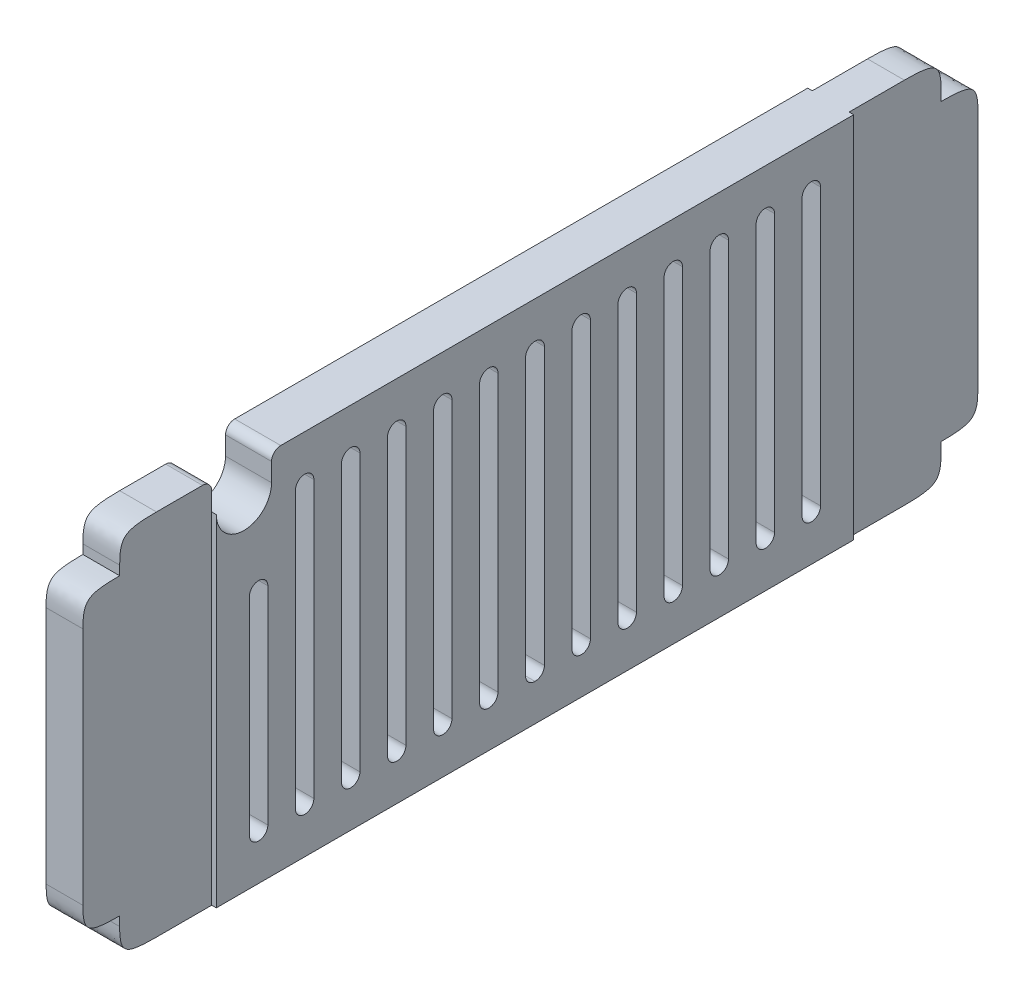
SolidWorks part; units mm, degrees
ref_plane "Front Plane" through (0, 0, 0) normal (0, 0, 1) x (1, 0, 0)
ref_plane "Top Plane" through (0, 0, 0) normal (0, 1, 0) x (1, 0, 0)
ref_plane "Right Plane" through (0, 0, 0) normal (1, 0, 0) x (0, 0, -1)
sketch "Sketch1" plane through (0, 0, 0) normal (0, 1, 0) x (1, 0, 0)
  line L0 (0, -6.35) -> (2.54, -6.35) construction
  line L1 (0, -6.35) -> (0, 0)
  line L2 (0, 0) -> (2.54, 0)
  line L3 (2.54, 0) -> (2.54, -6.35)
  line L4 (2.8575, -6.35) -> (2.54, -6.35)
  line L5 (0, -6.35) -> (-0.3175, -6.35)
  line L6 (-0.3175, -6.35) -> (-0.3175, -56.642)
  line L7 (2.8575, -6.35) -> (2.8575, -56.642)
  line L8 (-0.3175, -31.496) -> (2.8575, -31.496) construction
  line L9 (0, -56.642) -> (2.54, -56.642) construction
  line L10 (0, -56.642) -> (-0.3175, -56.642)
  line L11 (2.8575, -56.642) -> (2.54, -56.642)
  line L12 (2.54, -62.992) -> (2.54, -56.642)
  line L13 (0, -62.992) -> (2.54, -62.992)
  line L14 (0, -56.642) -> (0, -62.992)
  point P9 (1.27, -6.35)
  point P15 (1.27, -56.642)
  dimension "D1" = 3.175
  dimension "D2" = 0.3175
extrude "Boss-Extrude1" add sketch "Sketch1" along normal blind 25.4 contours L1 L2 L3 L4 L7 L11 L12 L13 L14 L10 L6 L5
sketch "Sketch2" plane through (2.54, 0, 0) normal (1, 0, 0) x (0, 0, -1)
  line L1 (-62.992, 22.86) -> (-62.992, 25.4) construction
  line L2 (-31.496, 25.4) -> (-31.496, 0) construction
  line L3 (-6.35, 25.4) -> (-56.642, 25.4) construction
  line L4 (-6.35, 0) -> (-56.642, 0) construction
  line L5 (-62.992, 22.86) -> (-65.532, 22.86)
  line L13 (-62.992, 2.54) -> (-62.992, 22.86)
  line L14 (-62.992, 25.4) -> (-62.992, 0) construction
  line L15 (-62.992, 2.54) -> (-62.992, 0) construction
  line L16 (-65.532, 22.86) -> (-65.532, 2.54)
  line L17 (-65.532, 2.54) -> (-62.992, 2.54)
  line L18 (0, 2.54) -> (0, 0) construction
  line L19 (0, 22.86) -> (0, 25.4) construction
  line L20 (2.54, 2.54) -> (0, 2.54)
  line L21 (2.54, 22.86) -> (2.54, 2.54)
  line L22 (0, 2.54) -> (0, 22.86)
  line L23 (0, 22.86) -> (2.54, 22.86)
  point P13 (-62.992, 12.7)
  point P23 (0, 12.7)
  line M9 (-62.992, 25.4) -> (-62.992, 0)
  dimension "D1" = 20.32
  dimension "D2" = 2.54
extrude "Boss-Extrude2" add sketch "Sketch2" against normal up to surface (2.54 mm away) contours M9 | L20 L22 L23 L21 region at (2.54, 12.7, 64.262) up to face at (0, 12.7, 59.817)
sketch "Sketch3" plane through (-0.3175, 0, 0) normal (-1, 0, 0) x (0, 0, 1)
  line L0 (31.496, 25.4) -> (31.496, 0) construction
  line L1 (6.35, 25.4) -> (56.642, 25.4) construction
  line L2 (6.35, 0) -> (56.642, 0) construction
  line L3 (31.496, 3.175) -> (31.496, 22.225) construction
  line L4 (31.496, 3.175) -> (31.496, 22.225) construction
  line L5 (30.861, 3.175) -> (30.861, 22.225)
  line L6 (32.131, 3.175) -> (32.131, 22.225)
  line L7 (35.306, 3.175) -> (35.306, 22.225)
  line L8 (34.036, 3.175) -> (34.036, 22.225)
  line L9 (34.671, 3.175) -> (34.671, 22.225) construction
  line L10 (38.481, 3.175) -> (38.481, 22.225)
  line L11 (37.211, 3.175) -> (37.211, 22.225)
  line L12 (37.846, 3.175) -> (37.846, 22.225) construction
  line L13 (41.656, 3.175) -> (41.656, 22.225)
  line L14 (40.386, 3.175) -> (40.386, 22.225)
  line L15 (41.021, 3.175) -> (41.021, 22.225) construction
  line L16 (44.831, 3.175) -> (44.831, 22.225)
  line L17 (43.561, 3.175) -> (43.561, 22.225)
  line L18 (44.196, 3.175) -> (44.196, 22.225) construction
  line L19 (48.006, 3.175) -> (48.006, 22.225)
  line L20 (46.736, 3.175) -> (46.736, 22.225)
  line L21 (47.371, 3.175) -> (47.371, 22.225) construction
  line L22 (51.181, 3.175) -> (51.181, 22.225)
  line L23 (49.911, 3.175) -> (49.911, 22.225)
  line L24 (50.546, 3.175) -> (50.546, 22.225) construction
  line L25 (54.356, 3.175) -> (54.356, 22.225)
  line L26 (53.086, 3.175) -> (53.086, 22.225)
  line L27 (53.721, 3.175) -> (53.721, 22.225) construction
  line L28 (28.321, 3.175) -> (28.321, 22.225) construction
  line L29 (27.686, 3.175) -> (27.686, 22.225)
  line L30 (28.956, 3.175) -> (28.956, 22.225)
  line L31 (25.146, 3.175) -> (25.146, 22.225) construction
  line L32 (24.511, 3.175) -> (24.511, 22.225)
  line L33 (25.781, 3.175) -> (25.781, 22.225)
  line L34 (21.971, 3.175) -> (21.971, 22.225) construction
  line L35 (21.336, 3.175) -> (21.336, 22.225)
  line L36 (22.606, 3.175) -> (22.606, 22.225)
  line L37 (18.796, 3.175) -> (18.796, 22.225) construction
  line L38 (18.161, 3.175) -> (18.161, 22.225)
  line L39 (19.431, 3.175) -> (19.431, 22.225)
  line L40 (15.621, 3.175) -> (15.621, 22.225) construction
  line L41 (14.986, 3.175) -> (14.986, 22.225)
  line L42 (16.256, 3.175) -> (16.256, 22.225)
  line L43 (12.446, 3.175) -> (12.446, 22.225) construction
  line L44 (11.811, 3.175) -> (11.811, 22.225)
  line L45 (13.081, 3.175) -> (13.081, 22.225)
  line L46 (9.271, 3.175) -> (9.271, 22.225) construction
  line L47 (8.636, 3.175) -> (8.636, 22.225)
  line L48 (9.906, 3.175) -> (9.906, 22.225)
  arc A0 (30.861, 3.175) -> (32.131, 3.175) centre (31.496, 3.175) ccw
  arc A1 (32.131, 22.225) -> (30.861, 22.225) centre (31.496, 22.225) ccw
  arc A2 (34.036, 3.175) -> (35.306, 3.175) centre (34.671, 3.175) ccw
  arc A3 (35.306, 22.225) -> (34.036, 22.225) centre (34.671, 22.225) ccw
  arc A4 (37.211, 3.175) -> (38.481, 3.175) centre (37.846, 3.175) ccw
  arc A5 (38.481, 22.225) -> (37.211, 22.225) centre (37.846, 22.225) ccw
  arc A6 (40.386, 3.175) -> (41.656, 3.175) centre (41.021, 3.175) ccw
  arc A7 (41.656, 22.225) -> (40.386, 22.225) centre (41.021, 22.225) ccw
  arc A8 (43.561, 3.175) -> (44.831, 3.175) centre (44.196, 3.175) ccw
  arc A9 (44.831, 22.225) -> (43.561, 22.225) centre (44.196, 22.225) ccw
  arc A10 (46.736, 3.175) -> (48.006, 3.175) centre (47.371, 3.175) ccw
  arc A11 (48.006, 22.225) -> (46.736, 22.225) centre (47.371, 22.225) ccw
  arc A12 (49.911, 3.175) -> (51.181, 3.175) centre (50.546, 3.175) ccw
  arc A13 (51.181, 22.225) -> (49.911, 22.225) centre (50.546, 22.225) ccw
  arc A14 (53.086, 3.175) -> (54.356, 3.175) centre (53.721, 3.175) ccw
  arc A15 (54.356, 22.225) -> (53.086, 22.225) centre (53.721, 22.225) ccw
  arc A16 (27.686, 3.175) -> (28.956, 3.175) centre (28.321, 3.175) ccw
  arc A17 (28.956, 22.225) -> (27.686, 22.225) centre (28.321, 22.225) ccw
  arc A18 (24.511, 3.175) -> (25.781, 3.175) centre (25.146, 3.175) ccw
  arc A19 (25.781, 22.225) -> (24.511, 22.225) centre (25.146, 22.225) ccw
  arc A20 (21.336, 3.175) -> (22.606, 3.175) centre (21.971, 3.175) ccw
  arc A21 (22.606, 22.225) -> (21.336, 22.225) centre (21.971, 22.225) ccw
  arc A22 (18.161, 3.175) -> (19.431, 3.175) centre (18.796, 3.175) ccw
  arc A23 (19.431, 22.225) -> (18.161, 22.225) centre (18.796, 22.225) ccw
  arc A24 (14.986, 3.175) -> (16.256, 3.175) centre (15.621, 3.175) ccw
  arc A25 (16.256, 22.225) -> (14.986, 22.225) centre (15.621, 22.225) ccw
  arc A26 (11.811, 3.175) -> (13.081, 3.175) centre (12.446, 3.175) ccw
  arc A27 (13.081, 22.225) -> (11.811, 22.225) centre (12.446, 22.225) ccw
  arc A28 (8.636, 3.175) -> (9.906, 3.175) centre (9.271, 3.175) ccw
  arc A29 (9.906, 22.225) -> (8.636, 22.225) centre (9.271, 22.225) ccw
  point P6 (31.496, 12.7)
  point P9 (31.496, 12.7)
  point P15 (28.321, 12.7)
  point P16 (34.671, 12.7)
  point P23 (37.846, 12.7)
  point P30 (41.021, 12.7)
  point P37 (44.196, 12.7)
  point P44 (47.371, 12.7)
  point P51 (50.546, 12.7)
  point P58 (53.721, 12.7)
  point P71 (25.146, 12.7)
  point P78 (21.971, 12.7)
  point P85 (18.796, 12.7)
  point P92 (15.621, 12.7)
  point P99 (12.446, 12.7)
  point P106 (9.271, 12.7)
  dimension "D1" = 19.05
  dimension "D2" = 1.27
  dimension "D4" = 3.175
  dimension "D6" = 3.175
  dimension "D3" = 8
  dimension "D5" = 8
extrude "Cut-Extrude1" cut sketch "Sketch3" against normal through all both and the other way through all
fillet "Fillet1" radius 1.905 4 edges at (1.27, 22.86, 65.532) (1.27, 2.54, -2.54) (1.27, 25.4, 62.992) (1.27, 0, 0) second distance 2.54 conic rho 0.65 first distance on face at (1.27, 12.7, 65.532) first distance on face at (1.27, 12.7, -2.54) first distance on face at (1.27, 24.13, 62.992) first distance on face at (1.27, 1.27, 0)
fillet "Fillet2" radius 2.54 4 edges at (1.27, 0, 62.992) (1.27, 2.54, 65.532) (1.27, 25.4, 0) (1.27, 22.86, -2.54) second distance 1.905 conic rho 0.65 first distance on face at (1.1642, 0, 31.9193) first distance on face at (1.27, 2.54, 64.262) first distance on face at (1.1642, 25.4, 31.0727) first distance on face at (1.27, 22.86, -1.27)
sketch "Sketch4" plane through (-0.3175, 0, 0) normal (-1, 0, 0) x (0, 0, 1)
  line L0 (6.35, 25.4) -> (25.146, 25.4) construction
  line L1 (6.35, 25.4) -> (56.642, 25.4) construction
  line L2 (25.146, 25.4) -> (25.146, 0)
  line L3 (6.35, 0) -> (56.642, 0) construction
  line L4 (25.146, 0) -> (68.2439, 0)
  line L5 (68.2439, 0) -> (68.2439, 25.4)
  line L6 (68.2439, 25.4) -> (25.146, 25.4)
  dimension "D1" = 18.796
extrude "Cut-Extrude2" cut sketch "Sketch4" against normal through all both and the other way through all
sketch "Sketch5" plane through (-0.3175, 0, 0) normal (-1, 0, 0) x (0, 0, 1)
  line L0 (25.146, 25.4) -> (25.146, 22.86) construction
  line L1 (21.336, 22.225) -> (21.336, 3.175) construction
  line L2 (22.606, 3.175) -> (22.606, 22.225) construction
  line L3 (21.336, 22.225) -> (21.336, 3.175)
  line L4 (22.606, 3.175) -> (22.606, 22.225)
  line L5 (18.161, 22.225) -> (18.161, 3.175)
  line L6 (19.431, 3.175) -> (19.431, 22.225)
  line L7 (6.35, 0) -> (25.146, 0)
  line L8 (25.146, 0) -> (25.146, 2.54)
  line L9 (24.511, 3.175) -> (24.511, 22.225)
  line L10 (25.146, 22.86) -> (25.146, 25.4)
  line L11 (25.146, 25.4) -> (6.35, 25.4)
  line L12 (6.35, 25.4) -> (6.35, 0)
  line L13 (6.35, 0) -> (43.942, 0)
  line L14 (25.146, 0) -> (25.146, 2.54)
  line L15 (24.511, 3.175) -> (24.511, 22.225)
  line L16 (25.146, 22.86) -> (25.146, 25.4)
  line L17 (43.942, 25.4) -> (6.35, 25.4)
  line L18 (6.35, 25.4) -> (6.35, 0)
  line L19 (14.986, 22.225) -> (14.986, 3.175)
  line L20 (16.256, 3.175) -> (16.256, 22.225)
  line L21 (11.811, 22.225) -> (11.811, 3.175)
  line L22 (13.081, 3.175) -> (13.081, 22.225)
  line L23 (8.636, 22.225) -> (8.636, 3.175)
  line L24 (9.906, 3.175) -> (9.906, 22.225)
  line L25 (40.386, 3.175) -> (40.386, 22.225)
  line L26 (41.656, 22.225) -> (41.656, 3.175)
  line L27 (37.211, 3.175) -> (37.211, 22.225)
  line L28 (38.481, 22.225) -> (38.481, 3.175)
  line L29 (34.036, 3.175) -> (34.036, 22.225)
  line L30 (35.306, 22.225) -> (35.306, 3.175)
  line L31 (43.942, 25.4) -> (43.942, 0)
  line L32 (25.781, 3.175) -> (25.781, 22.225)
  line L33 (30.861, 3.175) -> (30.861, 22.225)
  line L34 (32.131, 22.225) -> (32.131, 3.175)
  line L35 (27.686, 3.175) -> (27.686, 22.225)
  line L36 (28.956, 22.225) -> (28.956, 3.175)
  arc A0 (22.606, 22.225) -> (21.336, 22.225) centre (21.971, 22.225) ccw construction
  arc A1 (21.336, 3.175) -> (22.606, 3.175) centre (21.971, 3.175) ccw construction
  arc A2 (24.511, 3.175) -> (25.146, 2.54) centre (25.146, 3.175) ccw
  arc A3 (25.146, 22.86) -> (24.511, 22.225) centre (25.146, 22.225) ccw
  arc A4 (24.511, 3.175) -> (25.781, 3.175) centre (25.146, 3.175) ccw
  arc A5 (25.781, 22.225) -> (24.511, 22.225) centre (25.146, 22.225) ccw
  arc A6 (22.606, 22.225) -> (21.336, 22.225) centre (21.971, 22.225) ccw
  arc A7 (21.336, 3.175) -> (22.606, 3.175) centre (21.971, 3.175) ccw
  arc A8 (19.431, 22.225) -> (18.161, 22.225) centre (18.796, 22.225) ccw
  arc A9 (18.161, 3.175) -> (19.431, 3.175) centre (18.796, 3.175) ccw
  arc A10 (16.256, 22.225) -> (14.986, 22.225) centre (15.621, 22.225) ccw
  arc A11 (14.986, 3.175) -> (16.256, 3.175) centre (15.621, 3.175) ccw
  arc A12 (13.081, 22.225) -> (11.811, 22.225) centre (12.446, 22.225) ccw
  arc A13 (11.811, 3.175) -> (13.081, 3.175) centre (12.446, 3.175) ccw
  arc A14 (9.906, 22.225) -> (8.636, 22.225) centre (9.271, 22.225) ccw
  arc A15 (8.636, 3.175) -> (9.906, 3.175) centre (9.271, 3.175) ccw
  arc A16 (41.656, 3.175) -> (40.386, 3.175) centre (41.021, 3.175) cw
  arc A17 (40.386, 22.225) -> (41.656, 22.225) centre (41.021, 22.225) cw
  arc A18 (38.481, 3.175) -> (37.211, 3.175) centre (37.846, 3.175) cw
  arc A19 (37.211, 22.225) -> (38.481, 22.225) centre (37.846, 22.225) cw
  arc A20 (35.306, 3.175) -> (34.036, 3.175) centre (34.671, 3.175) cw
  arc A21 (34.036, 22.225) -> (35.306, 22.225) centre (34.671, 22.225) cw
  arc A22 (32.131, 3.175) -> (30.861, 3.175) centre (31.496, 3.175) cw
  arc A23 (30.861, 22.225) -> (32.131, 22.225) centre (31.496, 22.225) cw
  arc A24 (28.956, 3.175) -> (27.686, 3.175) centre (28.321, 3.175) cw
  arc A25 (27.686, 22.225) -> (28.956, 22.225) centre (28.321, 22.225) cw
  line M50 (25.146, 0) -> (25.146, 2.54)
  line M54 (25.146, 22.86) -> (25.146, 25.4)
  dimension "D3" = 1.905
  dimension "D1" = 0
  dimension "D2" = 5
extrude "Boss-Extrude3" add sketch "Sketch5" against normal up to surface (3.175 mm away) contours A5 L32 A4 L13 L31 L17 L25 A17 L26 A16 L27 A19 L28 A18 L29 A21 L30 A20 L33 A23 L34 A22 L35 A25 L36 A24 M50 M54 region at (-0.3175, 1.27, 25.462) up to face at (2.8575, 12.7, 20.2554)
sketch "Sketch7" plane through (2.54, 0, 0) normal (1, 0, 0) x (0, 0, -1)
  line L0 (-25.146, 25.4) -> (-25.146, 0) construction
  line L1 (-6.35, 25.4) -> (-43.942, 25.4) construction
  line L2 (-6.35, 0) -> (-43.942, 0) construction
  line L3 (-52.832, 4.445) -> (-52.832, 20.955)
  line L4 (-50.292, 1.905) -> (-50.292, 2.54)
  line L5 (-43.942, 0) -> (-47.752, 0)
  line L6 (0, 22.86) -> (0, 23.495)
  line L7 (-2.54, 25.4) -> (-6.35, 25.4)
  line L8 (-6.35, 25.4) -> (-6.35, 0)
  line L9 (-6.35, 0) -> (-2.54, 0)
  line L10 (0, 1.905) -> (0, 2.54)
  line L11 (2.54, 4.445) -> (2.54, 20.955)
  line L12 (0, 22.86) -> (0, 23.495)
  line L13 (-2.54, 25.4) -> (-6.35, 25.4)
  line L14 (-6.35, 25.4) -> (-6.35, 0)
  line L15 (-6.35, 0) -> (-2.54, 0)
  line L16 (0, 1.905) -> (0, 2.54)
  line L17 (2.54, 4.445) -> (2.54, 20.955)
  line L18 (-43.942, 25.4) -> (-43.942, 0)
  line L19 (-47.752, 25.4) -> (-43.942, 25.4)
  line L20 (-50.292, 22.86) -> (-50.292, 23.495)
  spline S0 degree 2 poles (-52.832, 20.955) (-52.832, 21.5663) (-52.7501, 21.9126) (-52.6865, 22.1813) (-52.561, 22.3519) (-52.4246, 22.5373) (-52.1842, 22.644) (-51.8674, 22.7847) (-51.2479, 22.8311) (-50.8627, 22.86) (-50.292, 22.86) knots 0 0 0 0.25 0.25 0.375 0.375 0.5 0.5 0.75 0.75 1 1 1
  spline S1 degree 2 poles (-50.292, 2.54) (-50.8585, 2.54) (-51.243, 2.5685) (-51.5105, 2.5884) (-51.7145, 2.6236) (-51.9898, 2.6712) (-52.1773, 2.753) (-52.4197, 2.8586) (-52.5582, 3.0444) (-52.6854, 3.2149) (-52.75, 3.487) (-52.832, 3.8326) (-52.832, 4.445) knots 0 0 0 0.25 0.25 0.375 0.375 0.5 0.5 0.625 0.625 0.75 0.75 1 1 1
  spline S2 degree 2 poles (-47.752, 0) (-48.3185, 0) (-48.703, 0.0285) (-48.9705, 0.0484) (-49.1745, 0.0836) (-49.4498, 0.1312) (-49.6373, 0.213) (-49.8797, 0.3186) (-50.0182, 0.5044) (-50.1454, 0.6749) (-50.21, 0.947) (-50.292, 1.2926) (-50.292, 1.905) knots 0 0 0 0.25 0.25 0.375 0.375 0.5 0.5 0.625 0.625 0.75 0.75 1 1 1
  spline S3 degree 2 poles (-50.292, 23.495) (-50.292, 24.1063) (-50.2101, 24.4526) (-50.1465, 24.7213) (-50.021, 24.8919) (-49.8846, 25.0773) (-49.6442, 25.184) (-49.3274, 25.3247) (-48.7079, 25.3711) (-48.3227, 25.4) (-47.752, 25.4) knots 0 0 0 0.25 0.25 0.375 0.375 0.5 0.5 0.75 0.75 1 1 1
  spline S4 degree 2 poles (-1140.7767, -3810.167) (9.6672, -16.7611) (-0.0819, 24.4526) (-0.1455, 24.7213) (-0.271, 24.8919) (-0.4074, 25.0773) (-0.6478, 25.184) (-0.9646, 25.3247) (-1.5841, 25.3711) (-57.0505, 29.5301) (-3958.5798, -565.1683) knots -29.501187 -29.501187 -29.501187 0.25 0.25 0.375 0.375 0.5 0.5 0.75 0.75 36.747836 36.747836 36.747836 only from (0, 23.495) to (-2.54, 25.4)
  spline S5 degree 2 poles (-3958.0281, 594.1974) (-57.4767, -4.1164) (-1.589, 0.0285) (-1.3215, 0.0484) (-1.1175, 0.0836) (-0.8422, 0.1312) (-0.6547, 0.213) (-0.4123, 0.3186) (-0.2738, 0.5044) (-0.1466, 0.6749) (-0.082, 0.947) (9.6475, 41.939) (-1134.6947, 3837.3785) knots -36.087343 -36.087343 -36.087343 0.25 0.25 0.375 0.375 0.5 0.5 0.625 0.625 0.75 0.75 30.403939 30.403939 30.403939 only from (-2.54, 0) to (0, 1.905)
  spline S6 degree 2 poles (-3955.4881, 596.7374) (-54.9367, -1.5764) (0.951, 2.5685) (1.2185, 2.5884) (1.4225, 2.6236) (1.6978, 2.6712) (1.8853, 2.753) (2.1277, 2.8586) (2.2662, 3.0444) (2.3934, 3.2149) (2.458, 3.487) (12.1875, 44.479) (-1132.1547, 3839.9185) knots -36.087343 -36.087343 -36.087343 0.25 0.25 0.375 0.375 0.5 0.5 0.625 0.625 0.75 0.75 30.403939 30.403939 30.403939 only from (0, 2.54) to (2.54, 4.445)
  spline S7 degree 2 poles (-1138.2367, -3812.707) (12.2072, -19.3011) (2.4581, 21.9126) (2.3945, 22.1813) (2.269, 22.3519) (2.1326, 22.5373) (1.8922, 22.644) (1.5754, 22.7847) (0.9559, 22.8311) (-54.5105, 26.9901) (-3956.0398, -567.7083) knots -29.501187 -29.501187 -29.501187 0.25 0.25 0.375 0.375 0.5 0.5 0.75 0.75 36.747836 36.747836 36.747836 only from (2.54, 20.955) to (0, 22.86)
  spline S8 degree 2 poles (0, 23.495) (0, 24.1063) (-0.0819, 24.4526) (-0.1455, 24.7213) (-0.271, 24.8919) (-0.4074, 25.0773) (-0.6478, 25.184) (-0.9646, 25.3247) (-1.5841, 25.3711) (-1.9693, 25.4) (-2.54, 25.4) knots 0 0 0 0.25 0.25 0.375 0.375 0.5 0.5 0.75 0.75 1 1 1
  spline S9 degree 2 poles (-2.54, 0) (-1.9735, 0) (-1.589, 0.0285) (-1.3215, 0.0484) (-1.1175, 0.0836) (-0.8422, 0.1312) (-0.6547, 0.213) (-0.4123, 0.3186) (-0.2738, 0.5044) (-0.1466, 0.6749) (-0.082, 0.947) (0, 1.2926) (0, 1.905) knots 0 0 0 0.25 0.25 0.375 0.375 0.5 0.5 0.625 0.625 0.75 0.75 1 1 1
  spline S10 degree 2 poles (0, 2.54) (0.5665, 2.54) (0.951, 2.5685) (1.2185, 2.5884) (1.4225, 2.6236) (1.6978, 2.6712) (1.8853, 2.753) (2.1277, 2.8586) (2.2662, 3.0444) (2.3934, 3.2149) (2.458, 3.487) (2.54, 3.8326) (2.54, 4.445) knots 0 0 0 0.25 0.25 0.375 0.375 0.5 0.5 0.625 0.625 0.75 0.75 1 1 1
  spline S11 degree 2 poles (2.54, 20.955) (2.54, 21.5663) (2.4581, 21.9126) (2.3945, 22.1813) (2.269, 22.3519) (2.1326, 22.5373) (1.8922, 22.644) (1.5754, 22.7847) (0.9559, 22.8311) (0.5707, 22.86) (0, 22.86) knots 0 0 0 0.25 0.25 0.375 0.375 0.5 0.5 0.75 0.75 1 1 1
  dimension "D1" = 0
extrude "Boss-Extrude4" add sketch "Sketch7" against normal up to surface (2.54 mm away) up to face at (0, 12.319, 1.651)
sketch "Sketch9" plane through (0, 25.4, 0) normal (0, 1, 0) x (1, 0, 0)
  line L0 (2.54, 2.54) -> (2.54, -31.5081) construction
  line L1 (2.54, -31.5081) -> (13.8841, -31.5081)
  line L2 (13.8841, -31.5081) -> (13.8841, -57.1564)
  line L3 (13.8841, -57.1564) -> (-12.4241, -57.1564)
  line L4 (-12.4241, -57.1564) -> (-12.4241, -31.5081)
  line L5 (-12.4241, -31.5081) -> (2.54, -31.5081)
  dimension "D1" = 34.0481
extrude "Cut-Extrude3" cut sketch "Sketch9" against normal through all
sketch "Sketch10" plane through (-0.3175, 0, 0) normal (-1, 0, 0) x (0, 0, 1)
  line L0 (27.686, 3.175) -> (27.686, 22.225) construction
  line L1 (28.956, 22.225) -> (28.956, 3.175) construction
  line L2 (27.686, 3.175) -> (27.686, 22.225)
  line L3 (28.956, 22.225) -> (28.956, 3.175)
  line L4 (24.511, 3.175) -> (24.511, 22.225)
  line L5 (25.781, 22.225) -> (25.781, 3.175)
  line L6 (6.35, 0) -> (31.5081, 0)
  line L7 (31.5081, 0) -> (31.5081, 2.5401)
  line L8 (30.861, 3.175) -> (30.861, 22.225)
  line L9 (31.5081, 22.8599) -> (31.5081, 25.4)
  line L10 (31.5081, 25.4) -> (6.35, 25.4)
  line L11 (6.35, 25.4) -> (6.35, 0)
  line L12 (6.35, 0) -> (56.6662, 0)
  line L13 (31.5081, 0) -> (31.5081, 2.5401)
  line L14 (30.861, 3.175) -> (30.861, 22.225)
  line L15 (31.5081, 22.8599) -> (31.5081, 25.4)
  line L16 (56.6662, 25.4) -> (6.35, 25.4)
  line L17 (6.35, 25.4) -> (6.35, 0)
  line L18 (21.336, 3.175) -> (21.336, 22.225)
  line L19 (22.606, 22.225) -> (22.606, 3.175)
  line L20 (18.161, 3.175) -> (18.161, 22.225)
  line L21 (19.431, 22.225) -> (19.431, 3.175)
  line L22 (14.986, 3.175) -> (14.986, 22.225)
  line L23 (16.256, 22.225) -> (16.256, 3.175)
  line L24 (11.811, 3.175) -> (11.811, 22.225)
  line L25 (13.081, 22.225) -> (13.081, 3.175)
  line L26 (8.636, 3.175) -> (8.636, 22.225)
  line L27 (9.906, 22.225) -> (9.906, 3.175)
  line L28 (53.1102, 22.225) -> (53.1102, 3.175)
  line L29 (54.3802, 3.175) -> (54.3802, 22.225)
  line L30 (49.9352, 22.225) -> (49.9352, 3.175)
  line L31 (51.2052, 3.175) -> (51.2052, 22.225)
  line L32 (46.7602, 22.225) -> (46.7602, 3.175)
  line L33 (48.0302, 3.175) -> (48.0302, 22.225)
  line L34 (43.5852, 22.225) -> (43.5852, 3.175)
  line L35 (44.8552, 3.175) -> (44.8552, 22.225)
  line L36 (40.4102, 22.225) -> (40.4102, 3.175)
  line L37 (41.6802, 3.175) -> (41.6802, 22.225)
  line L38 (37.2352, 22.225) -> (37.2352, 3.175)
  line L39 (38.5052, 3.175) -> (38.5052, 22.225)
  line L40 (34.0602, 22.225) -> (34.0602, 3.175)
  line L41 (35.3302, 3.175) -> (35.3302, 22.225)
  line L42 (56.6662, 25.4) -> (56.6662, 0)
  line L43 (32.1552, 3.175) -> (32.1552, 22.225)
  arc A0 (28.956, 22.225) -> (27.686, 22.225) centre (28.321, 22.225) ccw construction
  arc A1 (27.686, 3.175) -> (28.956, 3.175) centre (28.321, 3.175) ccw construction
  arc A2 (30.861, 3.175) -> (31.5081, 2.5401) centre (31.496, 3.175) ccw
  arc A3 (31.5081, 22.8599) -> (30.861, 22.225) centre (31.496, 22.225) ccw
  arc A4 (30.861, 3.175) -> (31.5081, 2.5401) centre (31.496, 3.175) ccw
  arc A5 (31.5081, 22.8599) -> (30.861, 22.225) centre (31.496, 22.225) ccw
  arc A6 (28.956, 22.225) -> (27.686, 22.225) centre (28.321, 22.225) ccw
  arc A7 (27.686, 3.175) -> (28.956, 3.175) centre (28.321, 3.175) ccw
  arc A8 (25.781, 22.225) -> (24.511, 22.225) centre (25.146, 22.225) ccw
  arc A9 (24.511, 3.175) -> (25.781, 3.175) centre (25.146, 3.175) ccw
  arc A10 (22.606, 22.225) -> (21.336, 22.225) centre (21.971, 22.225) ccw
  arc A11 (21.336, 3.175) -> (22.606, 3.175) centre (21.971, 3.175) ccw
  arc A12 (19.431, 22.225) -> (18.161, 22.225) centre (18.796, 22.225) ccw
  arc A13 (18.161, 3.175) -> (19.431, 3.175) centre (18.796, 3.175) ccw
  arc A14 (16.256, 22.225) -> (14.986, 22.225) centre (15.621, 22.225) ccw
  arc A15 (14.986, 3.175) -> (16.256, 3.175) centre (15.621, 3.175) ccw
  arc A16 (13.081, 22.225) -> (11.811, 22.225) centre (12.446, 22.225) ccw
  arc A17 (11.811, 3.175) -> (13.081, 3.175) centre (12.446, 3.175) ccw
  arc A18 (9.906, 22.225) -> (8.636, 22.225) centre (9.271, 22.225) ccw
  arc A19 (8.636, 3.175) -> (9.906, 3.175) centre (9.271, 3.175) ccw
  arc A20 (54.3802, 3.175) -> (53.1102, 3.175) centre (53.7452, 3.175) cw
  arc A21 (53.1102, 22.225) -> (54.3802, 22.225) centre (53.7452, 22.225) cw
  arc A22 (51.2052, 3.175) -> (49.9352, 3.175) centre (50.5702, 3.175) cw
  arc A23 (49.9352, 22.225) -> (51.2052, 22.225) centre (50.5702, 22.225) cw
  arc A24 (48.0302, 3.175) -> (46.7602, 3.175) centre (47.3952, 3.175) cw
  arc A25 (46.7602, 22.225) -> (48.0302, 22.225) centre (47.3952, 22.225) cw
  arc A26 (44.8552, 3.175) -> (43.5852, 3.175) centre (44.2202, 3.175) cw
  arc A27 (43.5852, 22.225) -> (44.8552, 22.225) centre (44.2202, 22.225) cw
  arc A28 (41.6802, 3.175) -> (40.4102, 3.175) centre (41.0452, 3.175) cw
  arc A29 (40.4102, 22.225) -> (41.6802, 22.225) centre (41.0452, 22.225) cw
  arc A30 (38.5052, 3.175) -> (37.2352, 3.175) centre (37.8702, 3.175) cw
  arc A31 (37.2352, 22.225) -> (38.5052, 22.225) centre (37.8702, 22.225) cw
  arc A32 (35.3302, 3.175) -> (34.0602, 3.175) centre (34.6952, 3.175) cw
  arc A33 (34.0602, 22.225) -> (35.3302, 22.225) centre (34.6952, 22.225) cw
  arc A34 (31.5081, 22.8599) -> (32.1552, 22.225) centre (31.5202, 22.225) cw
  arc A35 (32.1552, 3.175) -> (31.5081, 2.5401) centre (31.5202, 3.175) cw
  dimension "D3" = 1.905
  dimension "D1" = 0
  dimension "D2" = 7
extrude "Boss-Extrude5" add sketch "Sketch10" against normal up to surface (3.175 mm away) contours L42 L12 L17 L16 | L26 A18 L27 A19 | L24 A16 L25 A17 | L22 A14 L23 A15 | L20 A12 L21 A13 | L18 A10 L19 A11 | L4 A8 L5 A9 | A6 L2 A7 L3 | A20 L28 A21 L29 | A22 L30 A23 L31 | A24 L32 A25 L33 | A26 L34 A27 L35 | A28 L36 A29 L37 | A30 L38 A31 L39 | A32 L40 A33 L41 up to face at (2.8575, 12.7, 25.0235)
sketch "Sketch11" plane through (-0.3175, 0, 0) normal (-1, 0, 0) x (0, 0, 1)
  line L0 (27.686, 3.175) -> (27.686, 22.225) construction
  line L1 (28.956, 22.225) -> (28.956, 3.175) construction
  line L2 (27.686, 3.175) -> (27.686, 22.225)
  line L3 (28.956, 22.225) -> (28.956, 3.175)
  line L4 (32.131, 22.225) -> (32.131, 3.175)
  line L5 (30.861, 3.175) -> (30.861, 22.225)
  arc A0 (27.686, 3.175) -> (28.956, 3.175) centre (28.321, 3.175) ccw construction
  arc A1 (28.956, 22.225) -> (27.686, 22.225) centre (28.321, 22.225) ccw construction
  arc A2 (27.686, 3.175) -> (28.956, 3.175) centre (28.321, 3.175) ccw
  arc A3 (28.956, 22.225) -> (27.686, 22.225) centre (28.321, 22.225) ccw
  arc A4 (30.861, 3.175) -> (32.131, 3.175) centre (31.496, 3.175) ccw
  arc A5 (32.131, 22.225) -> (30.861, 22.225) centre (31.496, 22.225) ccw
  dimension "D2" = 1.905
  dimension "D1" = 2
extrude "Cut-Extrude4" cut sketch "Sketch11" against normal through all
sketch "Sketch12" plane through (0, 0, 0) normal (-1, 0, 0) x (0, 0, 1)
  line L0 (56.6662, 25.4) -> (56.6662, 0) construction
  line L1 (31.5081, 0) -> (31.5081, 25.4) construction
  line L2 (6.35, 0) -> (56.6662, 0) construction
  line L3 (6.35, 25.4) -> (56.6662, 25.4) construction
  line L4 (56.6662, 0) -> (56.6662, 25.4)
  line L5 (60.4762, 0) -> (56.6662, 0)
  line L6 (6.35, 25.4) -> (2.54, 25.4)
  line L7 (0, 23.495) -> (0, 22.86)
  line L8 (-2.54, 20.955) -> (-2.54, 4.445)
  line L9 (0, 2.54) -> (0, 1.905)
  line L10 (2.54, 0) -> (6.35, 0)
  line L11 (6.35, 0) -> (6.35, 25.4)
  line L12 (6.35, 25.4) -> (2.54, 25.4)
  line L13 (0, 23.495) -> (0, 22.86)
  line L14 (-2.54, 20.955) -> (-2.54, 4.445)
  line L15 (0, 2.54) -> (0, 1.905)
  line L16 (2.54, 0) -> (6.35, 0)
  line L17 (6.35, 0) -> (6.35, 25.4)
  line L18 (63.0162, 2.54) -> (63.0162, 1.905)
  line L19 (65.5562, 20.955) -> (65.5562, 4.445)
  line L20 (63.0162, 23.495) -> (63.0162, 22.86)
  line L21 (56.6662, 25.4) -> (60.4762, 25.4)
  spline S0 degree 2 poles (63.0162, 1.905) (63.0162, 1.2938) (62.9343, 0.9474) (62.8708, 0.6787) (62.7452, 0.5081) (62.6088, 0.3227) (62.3684, 0.216) (62.1827, 0.1335) (61.9072, 0.0851) (61.703, 0.0492) (61.4321, 0.0289) (61.047, 0) (60.4762, 0) knots 0 0 0 0.25 0.25 0.375 0.375 0.5 0.5 0.625 0.625 0.75 0.75 1 1 1
  spline S1 degree 2 poles (65.5562, 4.445) (65.5562, 3.8338) (65.4743, 3.4874) (65.4108, 3.2187) (65.2852, 3.0481) (65.1488, 2.8627) (64.9084, 2.756) (64.7227, 2.6735) (64.4472, 2.6251) (64.243, 2.5892) (63.9721, 2.5689) (63.587, 2.54) (63.0162, 2.54) knots 0 0 0 0.25 0.25 0.375 0.375 0.5 0.5 0.625 0.625 0.75 0.75 1 1 1
  spline S2 degree 2 poles (63.0162, 22.86) (63.5827, 22.86) (63.9672, 22.8315) (64.5833, 22.7858) (64.9016, 22.647) (65.1439, 22.5414) (65.2825, 22.3556) (65.4096, 22.1851) (65.4742, 21.913) (65.5562, 21.5674) (65.5562, 20.955) knots 0 0 0 0.25 0.25 0.5 0.5 0.625 0.625 0.75 0.75 1 1 1
  spline S3 degree 2 poles (60.4762, 25.4) (61.0427, 25.4) (61.4272, 25.3715) (62.0433, 25.3258) (62.3616, 25.187) (62.6039, 25.0814) (62.7425, 24.8956) (62.8696, 24.7251) (62.9342, 24.453) (63.0162, 24.1074) (63.0162, 23.495) knots 0 0 0 0.25 0.25 0.5 0.5 0.625 0.625 0.75 0.75 1 1 1
  spline S4 degree 2 poles (3957.9993, -568.8296) (57.479, 29.5165) (1.589, 25.3715) (0.9729, 25.3258) (0.6547, 25.187) (0.4123, 25.0814) (0.2738, 24.8956) (0.1466, 24.7251) (0.082, 24.453) (-9.6473, -16.5376) (1134.6606, -3812.0474) knots -36.08832 -36.08832 -36.08832 0.25 0.25 0.5 0.5 0.625 0.625 0.75 0.75 30.403498 30.403498 30.403498 only from (2.54, 25.4) to (0, 23.495)
  spline S5 degree 2 poles (3955.4593, -571.3696) (54.939, 26.9765) (-0.951, 22.8315) (-1.5671, 22.7858) (-1.8853, 22.647) (-2.1277, 22.5414) (-2.2662, 22.3556) (-2.3934, 22.1851) (-2.458, 21.913) (-12.1873, -19.0776) (1132.1206, -3814.5874) knots -36.08832 -36.08832 -36.08832 0.25 0.25 0.5 0.5 0.625 0.625 0.75 0.75 30.403498 30.403498 30.403498 only from (0, 22.86) to (-2.54, 20.955)
  spline S6 degree 2 poles (1138.4936, 3838.0156) (-12.2083, 44.7096) (-2.4581, 3.4874) (-2.3945, 3.2187) (-2.269, 3.0481) (-2.1326, 2.8627) (-1.8922, 2.756) (-1.7065, 2.6735) (-1.4309, 2.6251) (-1.2268, 2.5892) (-0.9559, 2.5689) (54.4976, -1.5894) (3956.0427, 592.9229) knots -29.504508 -29.504508 -29.504508 0.25 0.25 0.375 0.375 0.5 0.5 0.625 0.625 0.75 0.75 36.742225 36.742225 36.742225 only from (-2.54, 4.445) to (0, 2.54)
  spline S7 degree 2 poles (1141.0336, 3835.4756) (-9.6683, 42.1696) (0.0819, 0.9474) (0.1455, 0.6787) (0.271, 0.5081) (0.4074, 0.3227) (0.6478, 0.216) (0.8335, 0.1335) (1.1091, 0.0851) (1.3132, 0.0492) (1.5841, 0.0289) (57.0376, -4.1294) (3958.5827, 590.3829) knots -29.504508 -29.504508 -29.504508 0.25 0.25 0.375 0.375 0.5 0.5 0.625 0.625 0.75 0.75 36.742225 36.742225 36.742225 only from (0, 1.905) to (2.54, 0)
  spline S8 degree 2 poles (2.54, 25.4) (1.9735, 25.4) (1.589, 25.3715) (0.9729, 25.3258) (0.6547, 25.187) (0.4123, 25.0814) (0.2738, 24.8956) (0.1466, 24.7251) (0.082, 24.453) (0, 24.1074) (0, 23.495) knots 0 0 0 0.25 0.25 0.5 0.5 0.625 0.625 0.75 0.75 1 1 1
  spline S9 degree 2 poles (0, 22.86) (-0.5665, 22.86) (-0.951, 22.8315) (-1.5671, 22.7858) (-1.8853, 22.647) (-2.1277, 22.5414) (-2.2662, 22.3556) (-2.3934, 22.1851) (-2.458, 21.913) (-2.54, 21.5674) (-2.54, 20.955) knots 0 0 0 0.25 0.25 0.5 0.5 0.625 0.625 0.75 0.75 1 1 1
  spline S10 degree 2 poles (-2.54, 4.445) (-2.54, 3.8338) (-2.4581, 3.4874) (-2.3945, 3.2187) (-2.269, 3.0481) (-2.1326, 2.8627) (-1.8922, 2.756) (-1.7065, 2.6735) (-1.4309, 2.6251) (-1.2268, 2.5892) (-0.9559, 2.5689) (-0.5707, 2.54) (0, 2.54) knots 0 0 0 0.25 0.25 0.375 0.375 0.5 0.5 0.625 0.625 0.75 0.75 1 1 1
  spline S11 degree 2 poles (0, 1.905) (0, 1.2938) (0.0819, 0.9474) (0.1455, 0.6787) (0.271, 0.5081) (0.4074, 0.3227) (0.6478, 0.216) (0.8335, 0.1335) (1.1091, 0.0851) (1.3132, 0.0492) (1.5841, 0.0289) (1.9693, 0) (2.54, 0) knots 0 0 0 0.25 0.25 0.375 0.375 0.5 0.5 0.625 0.625 0.75 0.75 1 1 1
  dimension "D1" = 0
extrude "Boss-Extrude6" add sketch "Sketch12" against normal up to surface (2.54 mm away) up to face at (2.54, 13.208, 0.889)
sketch "Sketch13" plane through (0, 25.4, 0) normal (0, 1, 0) x (1, 0, 0)
  line L0 (-0.3175, -56.6662) -> (-0.3175, -34.6824) construction
  line L1 (-0.3175, -6.35) -> (-0.3175, -56.6662) construction
  dimension "D1" = 21.9838
sketch "Sketch14" plane through (0, 25.4, 0) normal (0, 1, 0) x (1, 0, 0)
  line L0 (-0.3175, -34.6824) -> (17.2064, -34.6824)
  line L2 (17.2064, -34.6824) -> (17.2064, 7.1642)
  line L3 (17.2064, 7.1642) -> (-50.8166, 7.1642)
  line L4 (-50.8166, 7.1642) -> (-0.3175, -34.6824)
extrude "Cut-Extrude5" cut sketch "Sketch14" against normal through all
sketch "Sketch15" plane through (-0.3175, 0, 0) normal (-1, 0, 0) x (0, 0, 1)
  line L0 (14.9845, 3.175) -> (14.9845, 22.225)
  line L1 (16.2545, 22.225) -> (16.2545, 3.175)
  line L2 (18.1595, 3.175) -> (18.1595, 22.225)
  line L3 (19.4295, 22.225) -> (19.4295, 3.175)
  line L4 (21.3345, 3.175) -> (21.3345, 22.225)
  line L5 (22.6045, 22.225) -> (22.6045, 3.175)
  line L6 (38.5052, 3.175) -> (38.5052, 22.225) construction
  line L7 (37.2352, 22.225) -> (37.2352, 3.175) construction
  line L8 (38.5052, 3.175) -> (38.5052, 22.225) construction
  line L9 (37.2352, 22.225) -> (37.2352, 3.175) construction
  line L10 (40.4102, 22.225) -> (40.4102, 3.175) construction
  line L11 (41.6802, 3.175) -> (41.6802, 22.225) construction
  line L12 (56.6662, 25.4) -> (34.6824, 25.4)
  line L13 (34.6824, 25.4) -> (34.6824, 22.8599)
  line L14 (35.3302, 22.225) -> (35.3302, 3.175)
  line L15 (34.6824, 2.5401) -> (34.6824, 0)
  line L16 (34.6824, 0) -> (56.6662, 0)
  line L17 (56.6662, 0) -> (56.6662, 25.4)
  line L18 (56.6662, 25.4) -> (12.6985, 25.4)
  line L19 (34.6824, 25.4) -> (34.6824, 22.8599)
  line L20 (35.3302, 22.225) -> (35.3302, 3.175) construction
  line L21 (34.6824, 2.5401) -> (34.6824, 0)
  line L22 (12.6985, 0) -> (56.6662, 0)
  line L23 (56.6662, 0) -> (56.6662, 25.4) construction
  line L24 (43.5852, 22.225) -> (43.5852, 3.175) construction
  line L25 (44.8552, 3.175) -> (44.8552, 22.225) construction
  line L26 (46.7602, 22.225) -> (46.7602, 3.175) construction
  line L27 (48.0302, 3.175) -> (48.0302, 22.225) construction
  line L28 (49.9352, 22.225) -> (49.9352, 3.175) construction
  line L29 (51.2052, 3.175) -> (51.2052, 22.225) construction
  line L30 (53.1102, 22.225) -> (53.1102, 3.175) construction
  line L31 (54.3802, 3.175) -> (54.3802, 22.225) construction
  line L32 (24.5095, 3.175) -> (24.5095, 22.225)
  line L33 (25.7795, 22.225) -> (25.7795, 3.175)
  line L34 (12.6985, 0) -> (12.6985, 25.4)
  line L35 (34.0345, 22.225) -> (34.0345, 3.175)
  line L36 (27.6845, 3.175) -> (27.6845, 22.225)
  line L37 (28.9545, 22.225) -> (28.9545, 3.175)
  line L38 (32.1295, 22.225) -> (32.1295, 3.175)
  line L39 (30.8595, 3.175) -> (30.8595, 22.225)
  arc A0 (16.2545, 3.175) -> (14.9845, 3.175) centre (15.6195, 3.175) cw
  arc A1 (14.9845, 22.225) -> (16.2545, 22.225) centre (15.6195, 22.225) cw
  arc A2 (38.5052, 22.225) -> (37.2352, 22.225) centre (37.8702, 22.225) ccw construction
  arc A3 (37.2352, 3.175) -> (38.5052, 3.175) centre (37.8702, 3.175) ccw construction
  arc A4 (35.3302, 22.225) -> (34.6824, 22.8599) centre (34.6952, 22.225) ccw
  arc A5 (34.6824, 2.5401) -> (35.3302, 3.175) centre (34.6952, 3.175) ccw
  arc A6 (35.3302, 22.225) -> (34.6824, 22.8599) centre (34.6952, 22.225) ccw construction
  arc A7 (34.6824, 2.5401) -> (35.3302, 3.175) centre (34.6952, 3.175) ccw construction
  arc A8 (38.5052, 22.225) -> (37.2352, 22.225) centre (37.8702, 22.225) ccw construction
  arc A9 (37.2352, 3.175) -> (38.5052, 3.175) centre (37.8702, 3.175) ccw construction
  arc A10 (41.6802, 22.225) -> (40.4102, 22.225) centre (41.0452, 22.225) ccw construction
  arc A11 (40.4102, 3.175) -> (41.6802, 3.175) centre (41.0452, 3.175) ccw construction
  arc A12 (44.8552, 22.225) -> (43.5852, 22.225) centre (44.2202, 22.225) ccw construction
  arc A13 (43.5852, 3.175) -> (44.8552, 3.175) centre (44.2202, 3.175) ccw construction
  arc A14 (48.0302, 22.225) -> (46.7602, 22.225) centre (47.3952, 22.225) ccw construction
  arc A15 (46.7602, 3.175) -> (48.0302, 3.175) centre (47.3952, 3.175) ccw construction
  arc A16 (51.2052, 22.225) -> (49.9352, 22.225) centre (50.5702, 22.225) ccw construction
  arc A17 (49.9352, 3.175) -> (51.2052, 3.175) centre (50.5702, 3.175) ccw construction
  arc A18 (54.3802, 22.225) -> (53.1102, 22.225) centre (53.7452, 22.225) ccw construction
  arc A19 (53.1102, 3.175) -> (54.3802, 3.175) centre (53.7452, 3.175) ccw construction
  arc A20 (19.4295, 3.175) -> (18.1595, 3.175) centre (18.7945, 3.175) cw
  arc A21 (18.1595, 22.225) -> (19.4295, 22.225) centre (18.7945, 22.225) cw
  arc A22 (22.6045, 3.175) -> (21.3345, 3.175) centre (21.9695, 3.175) cw
  arc A23 (21.3345, 22.225) -> (22.6045, 22.225) centre (21.9695, 22.225) cw
  arc A24 (25.7795, 3.175) -> (24.5095, 3.175) centre (25.1445, 3.175) cw
  arc A25 (24.5095, 22.225) -> (25.7795, 22.225) centre (25.1445, 22.225) cw
  arc A26 (28.9545, 3.175) -> (27.6845, 3.175) centre (28.3195, 3.175) cw
  arc A27 (27.6845, 22.225) -> (28.9545, 22.225) centre (28.3195, 22.225) cw
  arc A28 (32.1295, 3.175) -> (30.8595, 3.175) centre (31.4945, 3.175) cw
  arc A29 (30.8595, 22.225) -> (32.1295, 22.225) centre (31.4945, 22.225) cw
  arc A30 (34.6824, 2.5401) -> (34.0345, 3.175) centre (34.6695, 3.175) cw
  arc A31 (34.0345, 22.225) -> (34.6824, 22.8599) centre (34.6695, 22.225) cw
  line M84 (34.6824, 25.4) -> (34.6824, 22.8599)
  line M88 (34.6824, 2.5401) -> (34.6824, 0)
  dimension "D3" = 1.905
  dimension "D1" = 0
  dimension "D2" = 6
extrude "Boss-Extrude7" add sketch "Sketch15" against normal up to surface (3.175 mm away) contours L35 A31 L18 L34 L22 A30 L0 A1 L1 A0 L2 A21 L3 A20 L4 A23 L5 A22 L32 A25 L33 A24 L36 A27 L37 A26 L39 A29 L38 A28 M84 M88 region at (-0.3175, 12.7, 23.3893) up to face at (2.8575, 12.7, 40.3736)
sketch "Sketch16" plane through (2.54, 0, 0) normal (1, 0, 0) x (0, 0, -1)
  line L0 (-34.6824, 0) -> (-34.6824, 25.4) construction
  line L1 (-12.6985, 0) -> (-56.6662, 0) construction
  line L2 (-56.6662, 25.4) -> (-34.6824, 25.4) construction
  line L3 (-12.6985, 0) -> (-12.6985, 25.4)
  line L4 (-8.8885, 0) -> (-12.6985, 0)
  line L5 (-6.3485, 2.54) -> (-6.3485, 1.905)
  line L6 (-56.6662, 25.4) -> (-60.4762, 25.4)
  line L7 (-63.0162, 23.495) -> (-63.0162, 22.86)
  line L8 (-65.5562, 20.955) -> (-65.5562, 4.445)
  line L9 (-63.0162, 2.54) -> (-63.0162, 1.905)
  line L10 (-60.4762, 0) -> (-56.6662, 0)
  line L11 (-56.6662, 0) -> (-56.6662, 25.4)
  line L12 (-56.6662, 25.4) -> (-60.4762, 25.4)
  line L13 (-63.0162, 23.495) -> (-63.0162, 22.86)
  line L14 (-65.5562, 20.955) -> (-65.5562, 4.445)
  line L15 (-63.0162, 2.54) -> (-63.0162, 1.905)
  line L16 (-60.4762, 0) -> (-56.6662, 0)
  line L17 (-56.6662, 0) -> (-56.6662, 25.4)
  line L18 (-3.8085, 20.955) -> (-3.8085, 4.445)
  line L19 (-6.3485, 23.495) -> (-6.3485, 22.86)
  line L20 (-12.6985, 25.4) -> (-8.8885, 25.4)
  spline S0 degree 2 poles (-6.3485, 1.905) (-6.3485, 1.2938) (-6.4305, 0.9474) (-6.494, 0.6787) (-6.6195, 0.5081) (-6.7559, 0.3227) (-6.9963, 0.216) (-7.182, 0.1335) (-7.4576, 0.0851) (-7.6617, 0.0492) (-7.9326, 0.0289) (-8.3178, 0) (-8.8885, 0) knots 0 0 0 0.25 0.25 0.375 0.375 0.5 0.5 0.625 0.625 0.75 0.75 1 1 1
  spline S1 degree 2 poles (-3.8085, 4.445) (-3.8085, 3.8338) (-3.8905, 3.4874) (-3.954, 3.2187) (-4.0795, 3.0481) (-4.2159, 2.8627) (-4.4563, 2.756) (-4.642, 2.6735) (-4.9176, 2.6251) (-5.1217, 2.5892) (-5.3926, 2.5689) (-5.7778, 2.54) (-6.3485, 2.54) knots 0 0 0 0.25 0.25 0.375 0.375 0.5 0.5 0.625 0.625 0.75 0.75 1 1 1
  spline S2 degree 2 poles (-6.3485, 22.86) (-5.782, 22.86) (-5.3975, 22.8315) (-4.7814, 22.7858) (-4.4632, 22.647) (-4.2208, 22.5414) (-4.0823, 22.3556) (-3.9551, 22.1851) (-3.8906, 21.913) (-3.8085, 21.5674) (-3.8085, 20.955) knots 0 0 0 0.25 0.25 0.5 0.5 0.625 0.625 0.75 0.75 1 1 1
  spline S3 degree 2 poles (-8.8885, 25.4) (-8.322, 25.4) (-7.9375, 25.3715) (-7.3214, 25.3258) (-7.0032, 25.187) (-6.7608, 25.0814) (-6.6223, 24.8956) (-6.4951, 24.7251) (-6.4306, 24.453) (-6.3485, 24.1074) (-6.3485, 23.495) knots 0 0 0 0.25 0.25 0.5 0.5 0.625 0.625 0.75 0.75 1 1 1
  spline S4 degree 2 poles (3894.9831, -568.8296) (-5.5372, 29.5165) (-61.4272, 25.3715) (-62.0433, 25.3258) (-62.3616, 25.187) (-62.6039, 25.0814) (-62.7425, 24.8956) (-62.8696, 24.7251) (-62.9342, 24.453) (-72.6635, -16.5376) (1071.6444, -3812.0474) knots -36.08832 -36.08832 -36.08832 0.25 0.25 0.5 0.5 0.625 0.625 0.75 0.75 30.403498 30.403498 30.403498 only from (-60.4762, 25.4) to (-63.0162, 23.495)
  spline S5 degree 2 poles (3892.4431, -571.3696) (-8.0772, 26.9765) (-63.9672, 22.8315) (-64.5833, 22.7858) (-64.9016, 22.647) (-65.1439, 22.5414) (-65.2825, 22.3556) (-65.4096, 22.1851) (-65.4742, 21.913) (-75.2035, -19.0776) (1069.1044, -3814.5874) knots -36.08832 -36.08832 -36.08832 0.25 0.25 0.5 0.5 0.625 0.625 0.75 0.75 30.403498 30.403498 30.403498 only from (-63.0162, 22.86) to (-65.5562, 20.955)
  spline S6 degree 2 poles (1075.4774, 3838.0156) (-75.2245, 44.7096) (-65.4743, 3.4874) (-65.4108, 3.2187) (-65.2852, 3.0481) (-65.1488, 2.8627) (-64.9084, 2.756) (-64.7227, 2.6735) (-64.4472, 2.6251) (-64.243, 2.5892) (-63.9721, 2.5689) (-8.5186, -1.5894) (3893.0265, 592.9229) knots -29.504508 -29.504508 -29.504508 0.25 0.25 0.375 0.375 0.5 0.5 0.625 0.625 0.75 0.75 36.742225 36.742225 36.742225 only from (-65.5562, 4.445) to (-63.0162, 2.54)
  spline S7 degree 2 poles (1078.0174, 3835.4756) (-72.6845, 42.1696) (-62.9343, 0.9474) (-62.8708, 0.6787) (-62.7452, 0.5081) (-62.6088, 0.3227) (-62.3684, 0.216) (-62.1827, 0.1335) (-61.9072, 0.0851) (-61.703, 0.0492) (-61.4321, 0.0289) (-5.9786, -4.1294) (3895.5665, 590.3829) knots -29.504508 -29.504508 -29.504508 0.25 0.25 0.375 0.375 0.5 0.5 0.625 0.625 0.75 0.75 36.742225 36.742225 36.742225 only from (-63.0162, 1.905) to (-60.4762, 0)
  spline S8 degree 2 poles (-60.4762, 25.4) (-61.0427, 25.4) (-61.4272, 25.3715) (-62.0433, 25.3258) (-62.3616, 25.187) (-62.6039, 25.0814) (-62.7425, 24.8956) (-62.8696, 24.7251) (-62.9342, 24.453) (-63.0162, 24.1074) (-63.0162, 23.495) knots 0 0 0 0.25 0.25 0.5 0.5 0.625 0.625 0.75 0.75 1 1 1
  spline S9 degree 2 poles (-63.0162, 22.86) (-63.5827, 22.86) (-63.9672, 22.8315) (-64.5833, 22.7858) (-64.9016, 22.647) (-65.1439, 22.5414) (-65.2825, 22.3556) (-65.4096, 22.1851) (-65.4742, 21.913) (-65.5562, 21.5674) (-65.5562, 20.955) knots 0 0 0 0.25 0.25 0.5 0.5 0.625 0.625 0.75 0.75 1 1 1
  spline S10 degree 2 poles (-65.5562, 4.445) (-65.5562, 3.8338) (-65.4743, 3.4874) (-65.4108, 3.2187) (-65.2852, 3.0481) (-65.1488, 2.8627) (-64.9084, 2.756) (-64.7227, 2.6735) (-64.4472, 2.6251) (-64.243, 2.5892) (-63.9721, 2.5689) (-63.587, 2.54) (-63.0162, 2.54) knots 0 0 0 0.25 0.25 0.375 0.375 0.5 0.5 0.625 0.625 0.75 0.75 1 1 1
  spline S11 degree 2 poles (-63.0162, 1.905) (-63.0162, 1.2938) (-62.9343, 0.9474) (-62.8708, 0.6787) (-62.7452, 0.5081) (-62.6088, 0.3227) (-62.3684, 0.216) (-62.1827, 0.1335) (-61.9072, 0.0851) (-61.703, 0.0492) (-61.4321, 0.0289) (-61.047, 0) (-60.4762, 0) knots 0 0 0 0.25 0.25 0.375 0.375 0.5 0.5 0.625 0.625 0.75 0.75 1 1 1
  dimension "D1" = 0
extrude "Boss-Extrude8" add sketch "Sketch16" against normal up to surface (2.54 mm away) contours L3 L20 S3 L19 S2 L18 S1 L5 S0 L4 up to face at (0, 11.43, 61.7462)
sketch "Sketch17" plane through (-0.3175, 0, 0) normal (-1, 0, 0) x (0, 0, 1)
  line L0 (12.6985, 25.4) -> (56.6662, 25.4) construction
  line L1 (56.6662, 25.4) -> (56.6662, 0) construction
  line L2 (52.8562, 23.495) -> (52.8562, 25.4)
  line L3 (52.8562, 25.4) -> (56.6662, 25.4)
  line L4 (56.6662, 25.4) -> (56.6662, 23.495)
  circle A0 centre (54.7612, 23.495) radius 1.905 construction
  arc A1 (56.6662, 23.495) -> (52.8562, 23.495) centre (54.7612, 23.495) cw
  dimension "D1" = 3.81
extrude "Cut-Extrude6" cut sketch "Sketch17" against normal through all
sketch "Sketch18" plane through (-0.3175, 0, 0) normal (-1, 0, 0) x (0, 0, 1)
  line L0 (53.1102, 12.7) -> (53.1102, 22.225) construction
  line L1 (53.1102, 22.225) -> (53.1102, 3.175) construction
  line L2 (54.3802, 3.175) -> (54.3802, 21.6285) construction
  line L3 (53.1102, 22.225) -> (53.1102, 17.4625)
  line L4 (54.3802, 17.4625) -> (54.3802, 21.6285)
  arc A0 (53.1579, 22.4663) -> (54.3802, 21.6285) centre (54.7612, 23.495) ccw
  arc A2 (53.1102, 17.4625) -> (54.3802, 17.4625) centre (53.7452, 17.4625) cw
  arc A3 (53.1579, 22.4663) -> (53.1102, 22.225) centre (53.7452, 22.225) ccw construction
  arc A4 (53.1579, 22.4663) -> (53.1102, 22.225) centre (53.7452, 22.225) ccw
extrude "Boss-Extrude9" add sketch "Sketch18" against normal up to surface (3.175 mm away) up to face at (2.8575, 15.3876, 46.6307)
fillet "Fillet3" radius 0.635 2 edges at (1.27, 25.4, 56.6662) (1.27, 25.4, 52.8562)
